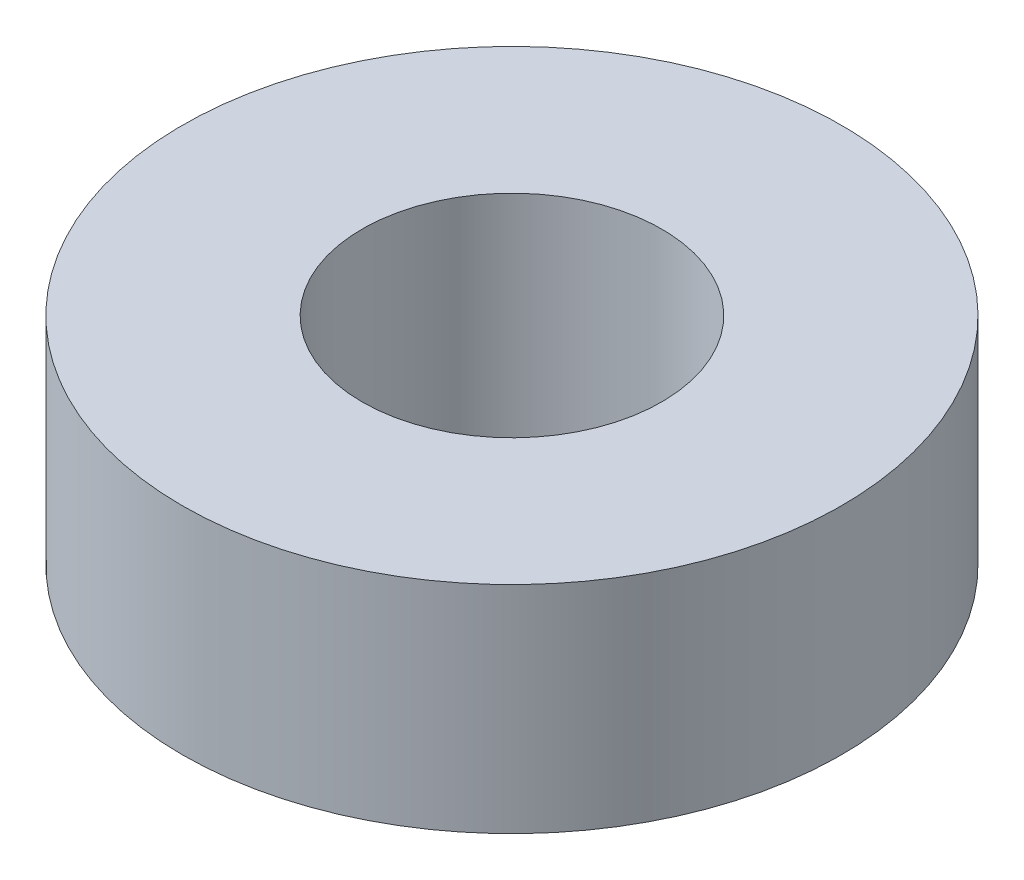
SolidWorks part; units mm, degrees
ref_plane "Front Plane" through (0, 0, 0) normal (0, 0, 1) x (1, 0, 0)
ref_plane "Top Plane" through (0, 0, 0) normal (0, 1, 0) x (1, 0, 0)
ref_plane "Right Plane" through (0, 0, 0) normal (1, 0, 0) x (0, 0, -1)
sketch "Sketch1" plane through (0, 0, 0) normal (0, 1, 0) x (1, 0, 0)
  circle A0 centre (0, 0) radius 27.5
  dimension "FLANGE_OD" = 55
extrude "Boss-Extrude1" add sketch "Sketch1" along normal blind 18
sketch "Sketch2" plane through (0, 0, 0) normal (0, 1, 0) x (1, 0, 0)
  circle A0 centre (0, 0) radius 12.5
  dimension "BORE_D" = 25
extrude "Cut-Extrude1" cut sketch "Sketch2" along normal through all
sketch "Sketch3" plane through (0, 18, 0) normal (0, 1, 0) x (1, 0, 0)
  circle A0 centre (0, 0) radius 9.788 construction
  circle A1 centre (-9.788, 0) radius 1.6583
  dimension "BOLT_D" = 3.3167
  dimension "BOLT_PCD" = 19.576
extrude "Cut-Extrude2" cut sketch "Sketch3" against normal blind 11.8565 rebuild error yes
pattern_circular "CirPattern1" count 8 over 360 rebuild error yes
